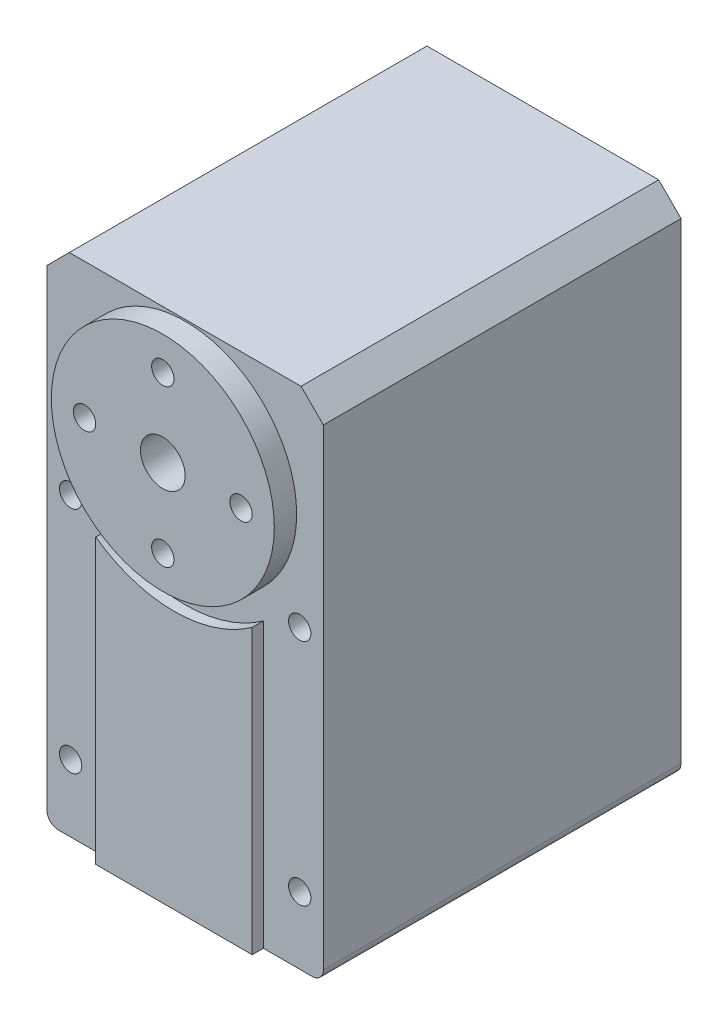
SolidWorks part; units mm, degrees
ref_plane "정면" through (0, 0, 0) normal (0, 0, 1) x (1, 0, 0)
ref_plane "윗면" through (0, 0, 0) normal (0, 1, 0) x (1, 0, 0)
ref_plane "우측면" through (0, 0, 0) normal (1, 0, 0) x (0, 0, -1)
sketch "스케치1" plane through (0, 0, 0) normal (0, 0, 1) x (1, 0, 0)
  line L1 (-12.365, 22.615) -> (12.365, 22.615)
  line L2 (-12.365, 22.615) -> (-12.365, -22.615)
  line L3 (-12.365, -22.615) -> (12.365, -22.615)
  line L4 (12.365, 22.615) -> (12.365, -22.615)
  line L5 (-12.365, 22.615) -> (12.365, -22.615) construction
  line L6 (-12.365, -22.615) -> (12.365, 22.615) construction
  point P0 (0, 0)
  dimension "D1" = 24.73
  dimension "D2" = 45.23
extrude "보스-돌출1" add sketch "스케치1" along normal blind 32
chamfer "모따기1" distance 2 angle 45 2 edges at (-12.365, 22.615, 16) (12.365, 22.615, 16)
sketch "스케치2" plane through (0, 0, 32) normal (0, 0, 1) x (1, 0, 0)
  line L0 (-12.365, -22.615) -> (12.365, -22.615) construction
  line L1 (-7, -22.615) -> (7, -22.615)
  line L2 (-7, -22.615) -> (-7, 2.7532)
  line L4 (7, -22.615) -> (7, 2.7532)
  arc A0 (-7, 2.7532) -> (7, 2.7532) centre (0, 12.5) ccw
  dimension "D4" = 24
  dimension "D1" = 14
  dimension "D2" = 7
  dimension "D3" = 12.5
extrude "보스-돌출2" add sketch "스케치2" along normal blind 1
sketch "스케치3" plane through (0, 0, 32) normal (0, 0, 1) x (1, 0, 0)
  line L0 (7, -22.615) -> (12.365, -22.615) construction
  line L1 (-10.25, -16.615) -> (10.25, -16.615) construction
  line L2 (-10.25, -16.615) -> (-10.25, 3.885) construction
  line L3 (-10.25, 3.885) -> (10.25, 3.885) construction
  line L4 (10.25, -16.615) -> (10.25, 3.885) construction
  circle A0 centre (-10.25, 3.885) radius 1
  circle A1 centre (-10.25, -16.615) radius 1
  circle A2 centre (10.25, -16.615) radius 1
  circle A3 centre (10.25, 3.885) radius 1
  dimension "D5" = 2
  dimension "D1" = 20.5
  dimension "D2" = 20.5
  dimension "D3" = 6
  dimension "D4" = 10.25
extrude "컷-돌출1" cut sketch "스케치3" against normal blind 4
sketch "스케치4" plane through (0, 0, 32) normal (0, 0, 1) x (1, 0, 0)
  circle A0 centre (0, 12.5) radius 9.975
  dimension "D1" = 12.5
  dimension "D2" = 19.95
extrude "보스-돌출3" add sketch "스케치4" along normal blind 2
sketch "스케치5" plane through (0, 0, 34) normal (0, 0, 1) x (1, 0, 0)
  circle A0 centre (0, 12.5) radius 7 construction
  circle A5 centre (0, 12.5) radius 2
  circle A6 centre (0, 19.5) radius 1
  circle A7 centre (7, 12.5) radius 1
  circle A8 centre (0, 12.5) radius 7 construction
  circle A9 centre (0, 5.5) radius 1
  circle A10 centre (0, 12.5) radius 7 construction
  circle A11 centre (-7, 12.5) radius 1
  circle A12 centre (0, 12.5) radius 7 construction
  point P18 (0, 12.5)
  dimension "D1" = 14
  dimension "D2" = 2
  dimension "D3" = 4
  dimension "D4" = 4
extrude "컷-돌출2" cut sketch "스케치5" against normal blind 3
sketch "스케치6" plane through (0, 0, 0) normal (0, 0, -1) x (-1, 0, 0)
  line L0 (-12.365, -22.615) -> (-12.365, 20.615) construction
  line L1 (-10.165, -18.115) -> (10.165, -18.115)
  line L2 (-10.165, -18.115) -> (-10.165, -6.115)
  line L3 (-10.165, -6.115) -> (10.165, -6.115)
  line L4 (10.165, -18.115) -> (10.165, -6.115)
  line L5 (12.365, 20.615) -> (12.365, -22.615) construction
  line L6 (12.365, -22.615) -> (-12.365, -22.615) construction
  dimension "D1" = 2.2
  dimension "D2" = 2.2
  dimension "D3" = 4.5
  dimension "D4" = 12
extrude "보스-돌출4" add sketch "스케치6" along normal blind 2
chamfer "모따기2" distance 2 angle 45 1 edges at (0, -6.115, -2)
sketch "스케치7" plane through (0, 0, 0) normal (0, 0, -1) x (-1, 0, 0)
  line L0 (12.365, 20.615) -> (12.365, -22.615) construction
  line L1 (11.165, -6.115) -> (-11.165, -6.115)
  line L2 (11.165, -6.115) -> (11.165, -1.115)
  line L3 (11.165, -1.115) -> (-11.165, -1.115)
  line L4 (-11.165, -6.115) -> (-11.165, -1.115)
  line L5 (-12.365, -22.615) -> (-12.365, 20.615) construction
  line L6 (10.165, -6.115) -> (-10.165, -6.115) construction
  dimension "D1" = 1.2
  dimension "D2" = 1.2
  dimension "D3" = 5
extrude "컷-돌출3" cut sketch "스케치7" against normal blind 2
sketch "스케치8" plane through (0, 0, 0) normal (0, 0, -1) x (-1, 0, 0)
  circle A0 centre (0, 12.5) radius 3
  dimension "D1" = 12.5
  dimension "D2" = 6
extrude "보스-돌출5" add sketch "스케치8" along normal blind 4.1
sketch "스케치9" plane through (0, 0, 0) normal (0, 0, -1) x (-1, 0, 0)
  line L0 (12.365, -22.615) -> (-12.365, -22.615) construction
  line L1 (-10.25, -20.615) -> (10.25, -20.615) construction
  line L2 (-10.25, -20.615) -> (-10.25, 3.885) construction
  line L3 (-10.25, 3.885) -> (10.25, 3.885) construction
  line L4 (10.25, -20.615) -> (10.25, 3.885) construction
  circle A0 centre (-10.25, 3.885) radius 1
  circle A1 centre (10.25, 3.885) radius 1
  circle A2 centre (-10.25, -20.615) radius 1
  circle A3 centre (10.25, -20.615) radius 1
  dimension "D5" = 2
  dimension "D1" = 20.5
  dimension "D2" = 24.5
  dimension "D3" = 10.25
  dimension "D4" = 2
extrude "컷-돌출4" cut sketch "스케치9" against normal blind 4
fillet "필렛1" radius 1 2 edges at (-12.365, -22.615, 16) (12.365, -22.615, 16)
